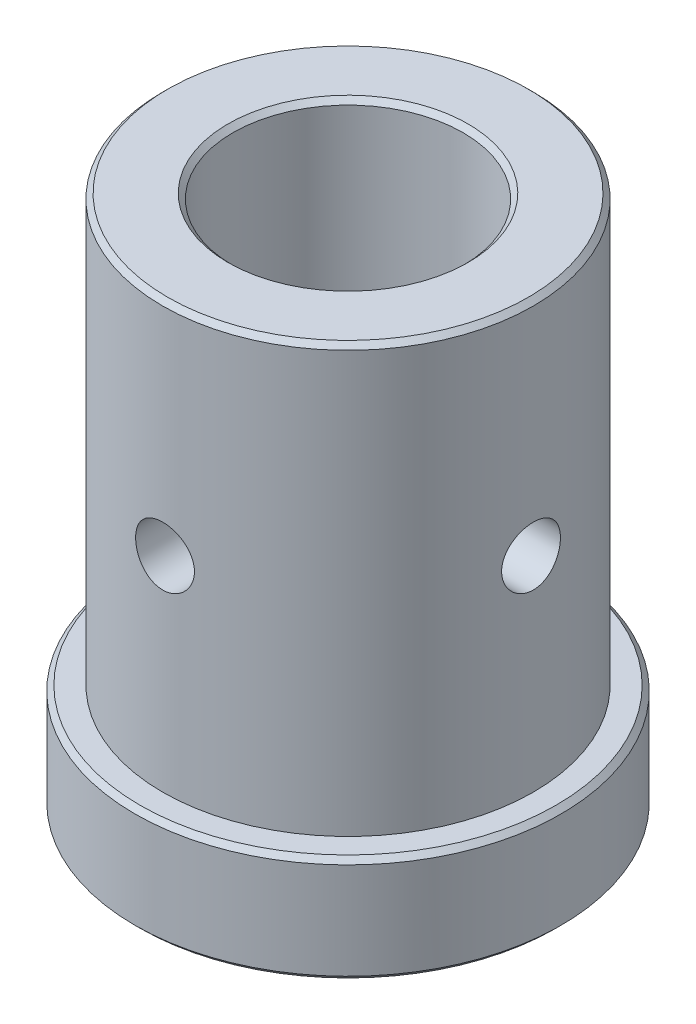
SolidWorks part; units mm, degrees
material "Nylon 101"
ref_plane "Front Plane" through (0, 0, 0) normal (0, 0, 1) x (1, 0, 0)
ref_plane "Top Plane" through (0, 0, 0) normal (0, 1, 0) x (1, 0, 0)
ref_plane "Right Plane" through (0, 0, 0) normal (1, 0, 0) x (0, 0, -1)
sketch "Sketch1" plane through (0, 0, 0) normal (0, 1, 0) x (1, 0, 0)
  circle A0 centre (0, 0) radius 11.049
  dimension "D1" = 22.098
extrude "Boss-Extrude1" add sketch "Sketch1" along normal blind 25.4
sketch "Sketch2" plane through (0, 0, 0) normal (0, -1, 0) x (1, 0, 0)
  circle A0 centre (0, 0) radius 12.7
  dimension "D1" = 25.4
extrude "Boss-Extrude2" add sketch "Sketch2" along normal blind 6.35
sketch "Sketch3" plane through (0, -6.35, 0) normal (0, -1, 0) x (1, 0, 0)
  circle A0 centre (0, 0) radius 6.858
  dimension "D1" = 13.716
extrude "Cut-Extrude1" cut sketch "Sketch3" against normal through all
sketch "Sketch4" plane through (0, -6.35, 0) normal (0, -1, 0) x (1, 0, 0)
  circle A0 centre (0, 0) radius 11.1125
  dimension "D1" = 22.225
ref_plane "Plane1" through (0, 9.525, 0) normal (0, 1, 0) x (1, 0, 0)
chamfer "Chamfer1" distance 0.3 angle 45 5 edges at (0, 0, -12.7) (0, -6.35, -12.7) (0, 25.4, 11.049) (0, 25.4, -6.858) (0, -6.35, -6.858)
sketch "Sketch5" plane through (0, 0, 0) normal (0, 0, 1) x (1, 0, 0)
  line L0 (12.4, 0) -> (-12.4, 0) construction
  circle A0 centre (0, 12.192) radius 1.7526
  point P2 (0, 0)
  dimension "D1" = 3.5052
  dimension "D2" = 12.192
extrude "Cut-Extrude2" cut sketch "Sketch5" against normal through all both and the other way through all
sketch "Sketch6" plane through (0, 0, 0) normal (1, 0, 0) x (0, 0, -1)
  line L0 (12.4, 0) -> (-12.4, 0) construction
  circle A0 centre (0, 12.192) radius 1.7526
  point P2 (0, 0)
  dimension "D1" = 3.5052
  dimension "D2" = 12.192
extrude "Cut-Extrude3" cut sketch "Sketch6" against normal through all both and the other way through all
equation "\"D1@Chamfer1\"=.3mm"
